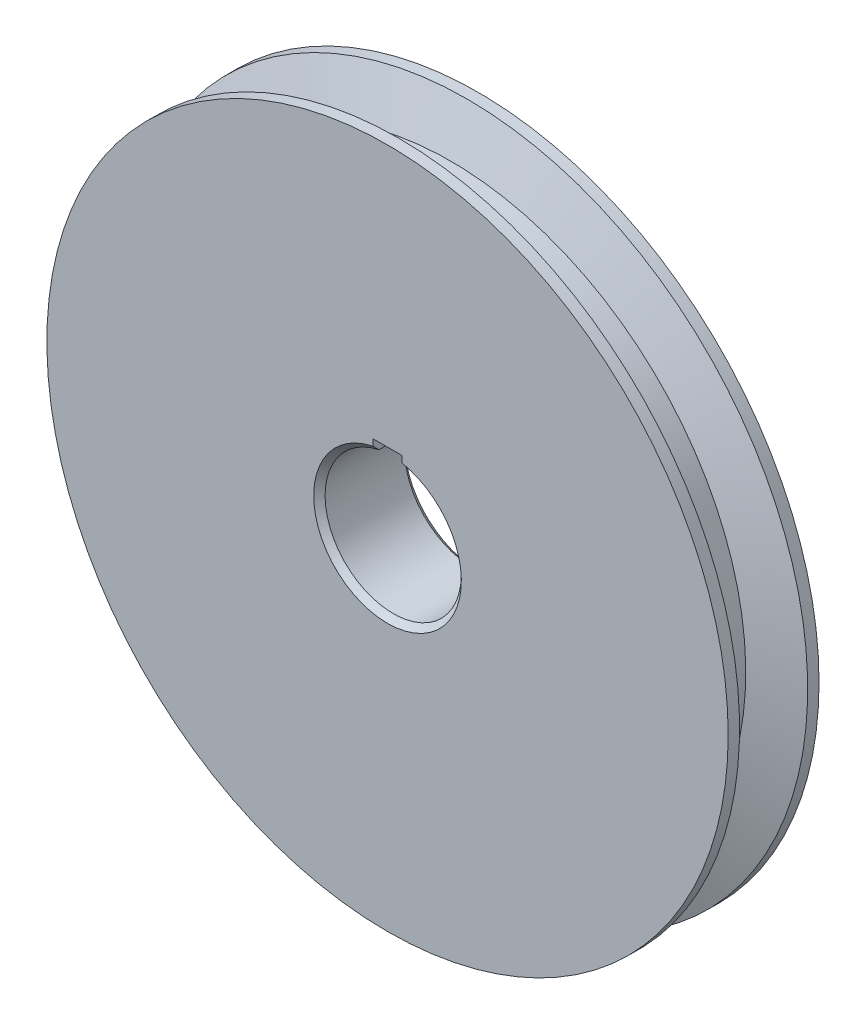
SolidWorks part; units mm, degrees
material "6061-T6 (SS)"
ref_plane "Front Plane" through (0, 0, 0) normal (0, 0, 1) x (1, 0, 0)
ref_plane "Top Plane" through (0, 0, 0) normal (0, 1, 0) x (1, 0, 0)
ref_plane "Right Plane" through (0, 0, 0) normal (1, 0, 0) x (0, 0, -1)
sketch "Sketch1" plane through (0, 0, 0) normal (0, 0, 1) x (1, 0, 0)
  circle A0 centre (0, 0) radius 47.625
  circle A1 centre (0, 0) radius 9.525
  dimension "D1" = 95.25
  dimension "D2" = 19.05
extrude "Extrude1" add sketch "Sketch1" along normal mid plane 12.7
sketch "Sketch2" plane through (0, 0, 0) normal (1, 0, 0) x (0, 0, -1)
  line L0 (-4.7625, 47.625) -> (4.7625, 47.625)
  line L2 (4.7625, 47.625) -> (2.4513, 41.275)
  line L3 (2.4513, 41.275) -> (-2.4513, 41.275)
  line L4 (-2.4513, 41.275) -> (-4.7625, 47.625)
  line L5 (-6.35, 0) -> (6.35, 0) construction
  line L6 (-6.35, 47.625) -> (-6.35, -47.625) construction
  line L7 (6.35, -47.625) -> (6.35, 47.625) construction
  point P2 (0, 47.625)
  point P5 (0, 41.275)
  dimension "D1" = 47.625
  dimension "D2" = 6.35
  dimension "D3" = 9.525
  dimension "D4" = 40
chamfer "Chamfer1" distance 0.7937 angle 45 2 edges at (9.525, 0, -6.35) (9.525, 0, 6.35)
revolve "Cut-Revolve1" cut sketch "Sketch2" angle 360 about L5
sketch "Sketch3" plane through (0, 0, 6.35) normal (0, 0, 1) x (1, 0, 0)
  line L0 (0, 0) -> (0, 9.525) construction
  line L2 (-2, 11.025) -> (2, 11.025)
  line L3 (-2, 11.025) -> (-2, 8.025)
  line L4 (-2, 8.025) -> (2, 8.025)
  line L5 (2, 11.025) -> (2, 8.025)
  line L6 (-2, 11.025) -> (2, 8.025) construction
  line L7 (-2, 8.025) -> (2, 11.025) construction
  circle A0 centre (0, 0) radius 9.525 construction
  dimension "D1" = 4
  dimension "D2" = 3
extrude "Cut-Extrude1" cut sketch "Sketch3" against normal through all contours L4 L5 L2 L3
